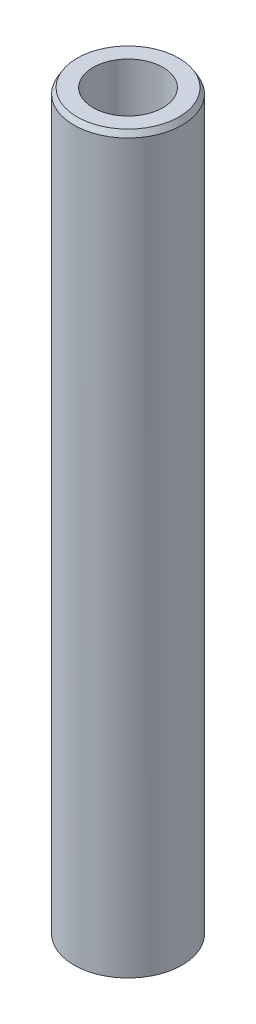
SolidWorks part; units mm, degrees
ref_plane "Front Plane" through (0, 0, 0) normal (0, 0, 1) x (1, 0, 0)
ref_plane "Top Plane" through (0, 0, 0) normal (0, 1, 0) x (1, 0, 0)
ref_plane "Right Plane" through (0, 0, 0) normal (1, 0, 0) x (0, 0, -1)
sketch "Sketch1" plane through (0, 0, 0) normal (0, 1, 0) x (1, 0, 0)
  circle A0 centre (0, 0) radius 7.5
  dimension "SHAFT_OD" = 15
extrude "Boss-Extrude1" add sketch "Sketch1" along normal blind 102.0492
sketch "Sketch2" plane through (0, 0, 0) normal (0, 1, 0) x (1, 0, 0)
  circle A0 centre (0, 0) radius 4.8457
  dimension "BORE_D" = 9.6914
extrude "Cut-Extrude1" cut sketch "Sketch2" along normal through all
chamfer "Chamfer1" distance 0.7626 angle 30 2 edges at (0, 102.0492, 7.5) (0, 0, 7.5) first distance on face at (0, 102.0492, 7.5) first distance on face at (0, 0, 4.8457)
